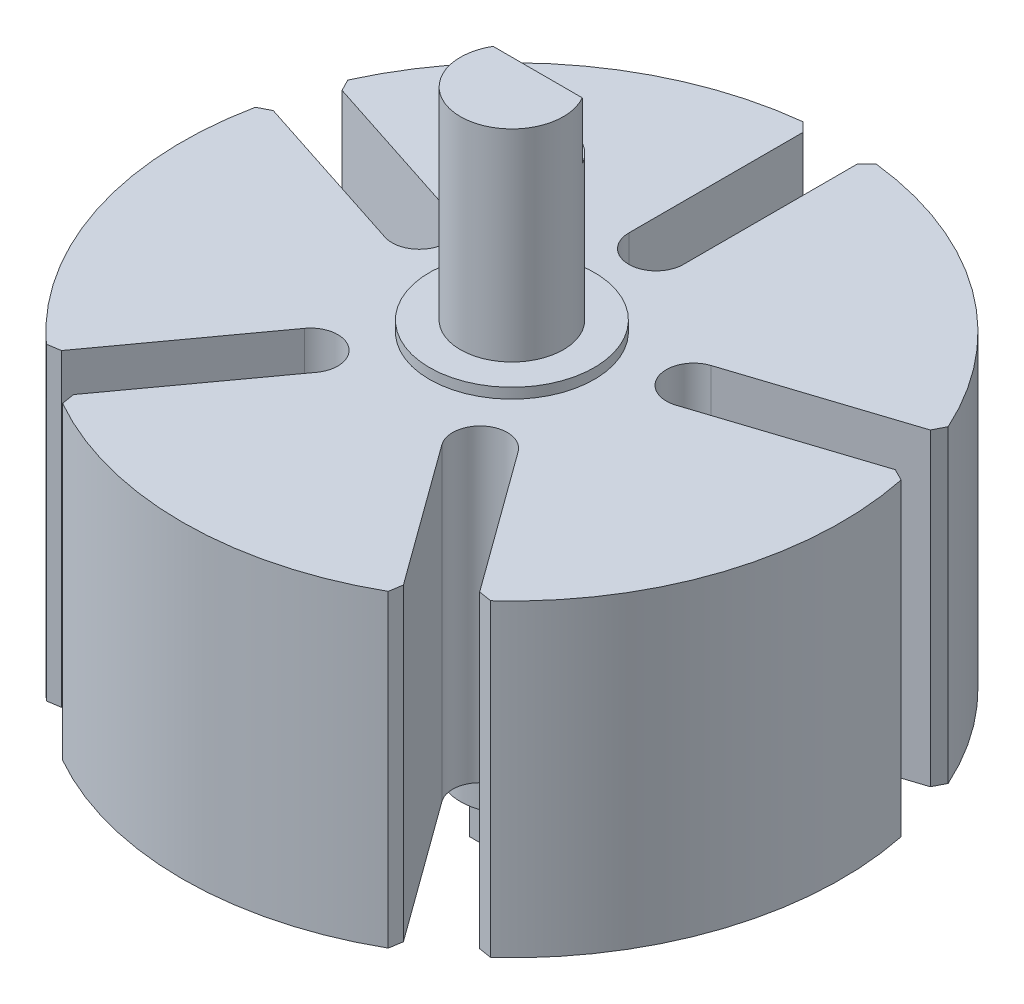
SolidWorks part; units mm, degrees
ref_plane "前视基准面" through (0, 0, 0) normal (0, 0, 1) x (1, 0, 0)
ref_plane "上视基准面" through (0, 0, 0) normal (0, 1, 0) x (1, 0, 0)
ref_plane "右视基准面" through (0, 0, 0) normal (1, 0, 0) x (0, 0, -1)
sketch "草图1" plane through (0, 0, 0) normal (0, 1, 0) x (1, 0, 0)
  circle A0 centre (0, 0) radius 16
  dimension "D1" = 32
extrude "凸台-拉伸1" add sketch "草图1" along normal blind 15
sketch "草图2" plane through (0, 15, 0) normal (0, 1, 0) x (1, 0, 0)
  circle A0 centre (0, 0) radius 4
  dimension "D1" = 8
extrude "凸台-拉伸2" add sketch "草图2" along normal blind 0.5
sketch "草图3" plane through (0, 0, 0) normal (0, -1, 0) x (1, 0, 0)
  circle A0 centre (0, 0) radius 4
  dimension "D1" = 8
extrude "凸台-拉伸3" add sketch "草图3" along normal blind 0.5
sketch "草图4" plane through (0, 15.5, 0) normal (0, 1, 0) x (1, 0, 0)
  circle A0 centre (0, 0) radius 2.5
  dimension "D1" = 5
extrude "凸台-拉伸4" add sketch "草图4" along normal blind 9.8
sketch "草图5" plane through (0, -0.5, 0) normal (0, -1, 0) x (1, 0, 0)
  circle A0 centre (0, 0) radius 2.5
  dimension "D1" = 5
extrude "凸台-拉伸5" add sketch "草图5" along normal blind 3
sketch "草图6" plane through (0, 25.3, 0) normal (0, 1, 0) x (1, 0, 0)
  line L0 (-2.1651, 1.25) -> (2.1651, 1.25)
  line L1 (-2.1651, 1.25) -> (0, 0) construction
  line L2 (0, 0) -> (2.1651, 1.25) construction
  circle A0 centre (0, 0) radius 2.5 construction
  circle A2 centre (0, 0) radius 2.5
  arc A3 (2.1651, 1.25) -> (-2.1651, 1.25) centre (0, 0) ccw
  dimension "D1" = 120
  dimension "D2" = 0
extrude "切除-拉伸1" cut sketch "草图6" against normal blind 2.8
sketch "草图7" plane through (0, 15, 0) normal (0, 1, 0) x (1, 0, 0)
  line L0 (0, 0) -> (0, 16.218) construction
  line L1 (-1.325, 7) -> (-1.325, 19)
  line L2 (-1.325, 19) -> (1.325, 19)
  line L3 (1.325, 19) -> (1.325, 7)
  line L4 (0, 16) -> (2.9481, 16) construction
  circle A0 centre (0, 7) radius 1.325 construction
  circle A2 centre (0, 0) radius 16 construction
  arc A3 (1.325, 7) -> (-1.325, 7) centre (0, 7) cw
  dimension "D1" = 2.65
  dimension "D2" = 3
  dimension "D3" = 7
extrude "切除-拉伸2" cut sketch "草图7" against normal through all
pattern_circular "阵列(圆周)1" count 5 over 360 about axis through (0, 25.3, 0) along (0, -1, 0) of "切除-拉伸2" reverse direction yes
sketch "草图8" plane through (0, -3.5, 0) normal (0, -1, 0) x (1, 0, 0)
  circle A0 centre (0, 0) radius 1.5
  dimension "D1" = 3
extrude "凸台-拉伸6" add sketch "草图8" along normal blind 3
chamfer "倒角1" distance 0.5 angle 45 10 edges at (-15.5741, 7.5, -3.6671) (-14.7552, 7.5, -6.1874) (-10.4442, 7.5, 12.121) (-8.3003, 7.5, 13.6786) (8.3003, 7.5, 13.6786) (10.4442, 7.5, 12.121) (15.5741, 7.5, -3.6671) (14.7552, 7.5, -6.1874) (1.325, 7.5, -15.945) (-1.325, 7.5, -15.945) first distance on face at (-11.3205, 7.5, -2.2851) first distance on face at (-10.5016, 7.5, -4.8054) first distance on face at (-7.8153, 7.5, 8.5026) first distance on face at (-5.6714, 7.5, 10.0603) first distance on face at (5.6714, 7.5, 10.0603) first distance on face at (7.8153, 7.5, 8.5026) first distance on face at (11.3205, 7.5, -2.2851) first distance on face at (10.5016, 7.5, -4.8054) first distance on face at (1.325, 7.5, -11.4725) first distance on face at (-1.325, 7.5, -11.4725)
sketch "草图9" plane through (0, -6.5, 0) normal (0, -1, 0) x (1, 0, 0)
  line L0 (-1.299, 0.75) -> (1.299, 0.75)
  line L1 (0, 0) -> (-1.299, 0.75) construction
  line L2 (1.299, 0.75) -> (0, 0) construction
  circle A0 centre (0, 0) radius 1.5 construction
  arc A1 (1.299, 0.75) -> (-1.299, 0.75) centre (0, 0) ccw
  dimension "D1" = 120
extrude "切除-拉伸3" cut sketch "草图9" against normal blind 3
